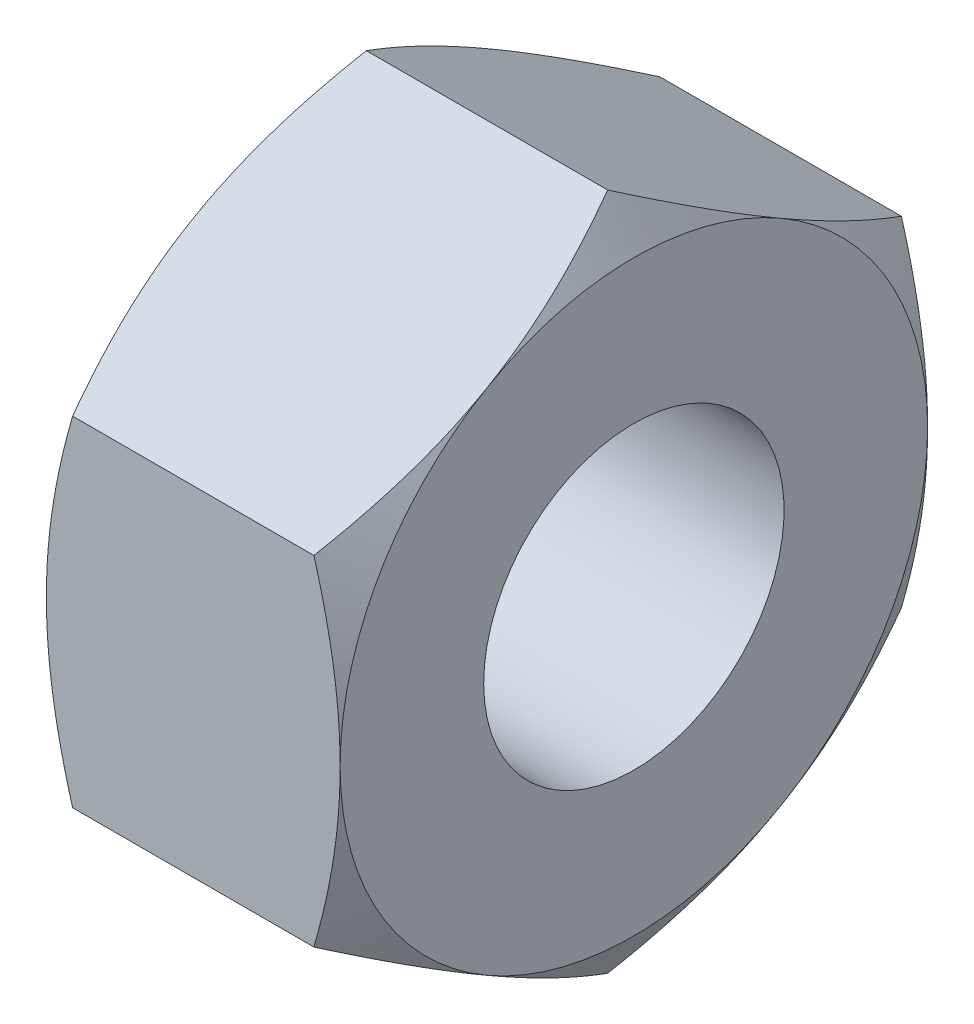
SolidWorks part; units mm, degrees
ref_plane "Front Plane" through (0, 0, 0) normal (0, 0, 1) x (1, 0, 0)
ref_plane "Top Plane" through (0, 0, 0) normal (0, 1, 0) x (1, 0, 0)
ref_plane "Right Plane" through (0, 0, 0) normal (1, 0, 0) x (0, 0, -1)
ref_axis "Axis_X" through (-0.325, 0, 0) along (1, 0, 0)
ref_axis "Axis_Y" through (0, 8.2561, 0) along (0, -1, 0)
ref_axis "Axis_Z" through (0, 0, -7.15) along (0, 0, 1)
sketch "Sketch1" plane through (0, 0, 0) normal (1, 0, 0) x (0, 0, -1)
  line L1 (6.5, -3.7528) -> (6.5, 3.7528)
  line L2 (6.5, 3.7528) -> (0, 7.5056)
  line L3 (0, 7.5056) -> (-6.5, 3.7528)
  line L4 (-6.5, 3.7528) -> (-6.5, -3.7528)
  line L5 (-6.5, -3.7528) -> (0, -7.5056)
  line L6 (0, -7.5056) -> (6.5, -3.7528)
  circle A0 centre (0, 0) radius 6.5 construction
  dimension "B" = 13
extrude "Boss-Extrude1" add sketch "Sketch1" along normal blind 6.5
sketch "Sketch2" plane through (0, 0, 0) normal (0, 0, 1) x (1, 0, 0)
  line L0 (6.5, 7.5056) -> (6.5, 6.5)
  line L1 (6.5, 6.5) -> (5.9194, 7.5056)
  line L2 (5.9194, 7.5056) -> (6.5, 7.5056)
  line L3 (0, 7.5056) -> (0.5806, 7.5056)
  line L5 (0, 7.5056) -> (0, 6.5)
  line L6 (0, 6.5) -> (0.5806, 7.5056)
  line L9 (6.5, 7.5056) -> (0, 7.5056) construction
  dimension "FIX_1" = 30
revolve "Cut-Revolve1" cut sketch "Sketch2" angle 360 about axis through (-0.325, 0, 0) along (1, 0, 0)
hole_wizard "Tap1" positions "Sketch4" profile "Sketch3" hole size "M10x1.5" standard "JIS" end condition through all
sketch "Sketch4" plane through (0, 0, 0) normal (1, 0, 0) x (0, 0, -1)
  point P0 (0, 0)
sketch "Sketch3" plane through (0, 0, 0) normal (0, 1, 0) x (0, 0, 1)
  line L0 (0, 0) -> (0, 6.5)
  line L1 (0, 6.5) -> (3.3235, 6.5)
  line L2 (3.3235, 6.5) -> (3.3235, 0)
  line L5 (3.3235, 0) -> (0, 0)
  line L11 (0, -6.35) -> (0, 107.95) construction
  dimension "HSD_1" = 6.647
  dimension "Thru Hole Depth" = 6.5
cosmetic thread "Thread1" parameters "M"=8
equation "\"Factor\"= 1.082532"
